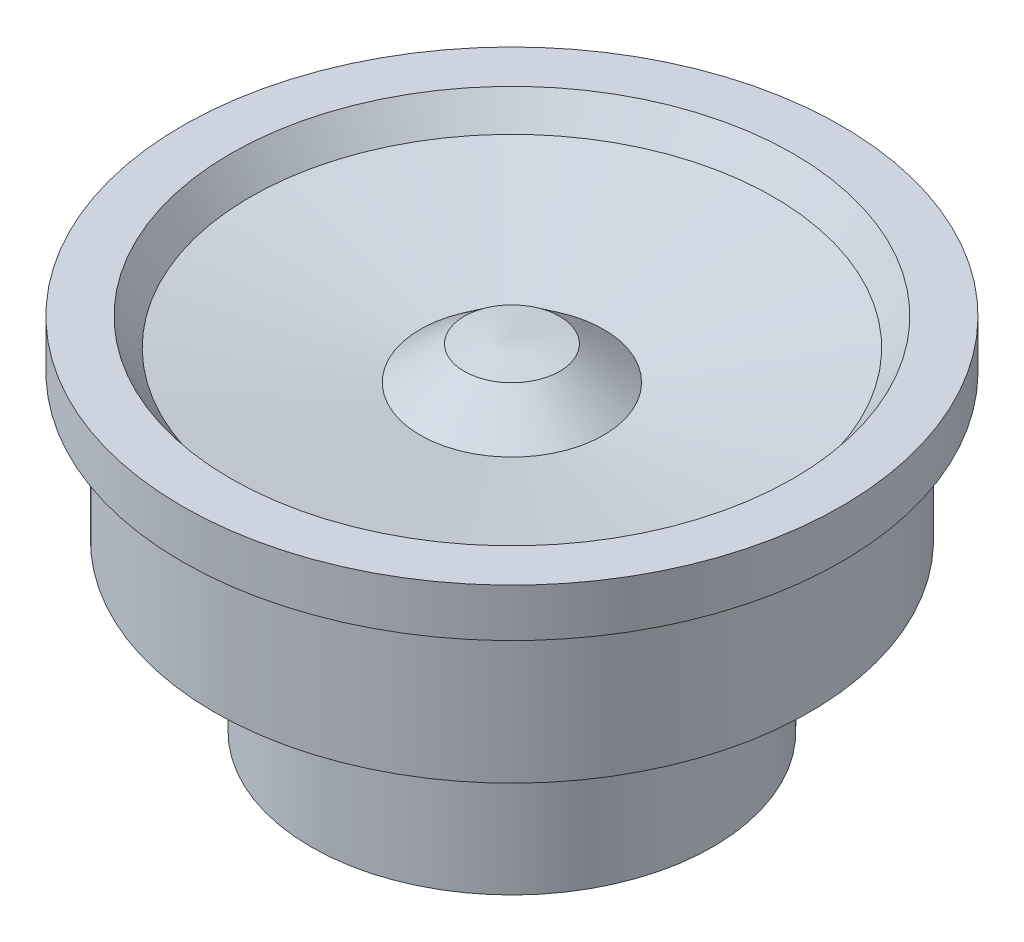
SolidWorks part; units mm, degrees
ref_plane "Front Plane" through (0, 0, 0) normal (0, 0, 1) x (1, 0, 0)
ref_plane "Top Plane" through (0, 0, 0) normal (0, 1, 0) x (1, 0, 0)
ref_plane "Right Plane" through (0, 0, 0) normal (1, 0, 0) x (0, 0, -1)
sketch "Sketch1" plane through (0, 0, 0) normal (0, 0, 1) x (1, 0, 0)
  line L0 (0, 0) -> (12.125, 0)
  line L1 (12.125, 0) -> (12.125, 10)
  line L2 (19.9, 18.8) -> (18, 18.8)
  line L3 (19.9, 18.8) -> (19.9, 21.7)
  line L4 (19.9, 21.7) -> (0, 21.7) construction
  line L5 (18, 18.8) -> (18, 10)
  line L6 (18, 10) -> (12.125, 10)
  line L7 (0, 21.7) -> (0, 0) construction
  line L8 (0, 0) -> (0, 21.7) construction
  line L9 (19.9, 21.7) -> (16.9892, 21.7)
  line L10 (16.9892, 21.7) -> (15.7871, 20.0424)
  line L11 (15.7871, 20.0424) -> (5.5379, 18.2393)
  line L12 (5.5379, 18.2393) -> (2.8808, 20.25)
  line L13 (2.8808, 20.25) -> (0, 20.6118)
  line L14 (0, 20.6118) -> (0, 0)
  dimension "D1" = 12.125
  dimension "D2" = 21.7
  dimension "D3" = 2.9
  dimension "D4" = 18
  dimension "D5" = 19.9
  dimension "D6" = 10
revolve "Revolve1" add sketch "Sketch1" angle 360 about L7
